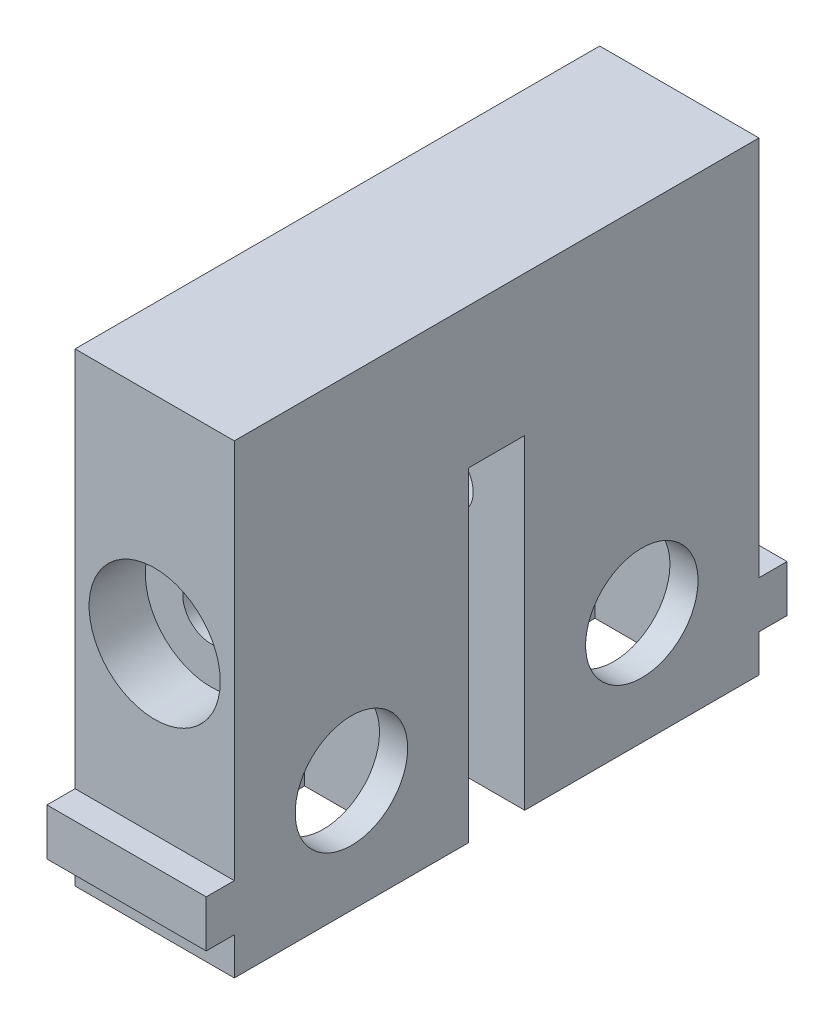
SolidWorks part; units mm, degrees
material "ABS"
ref_plane "Front Plane" through (0, 0, 0) normal (0, 0, 1) x (1, 0, 0)
ref_plane "Top Plane" through (0, 0, 0) normal (0, 1, 0) x (1, 0, 0)
ref_plane "Right Plane" through (0, 0, 0) normal (1, 0, 0) x (0, 0, -1)
sketch "Sketch1" plane through (0, 0, 0) normal (1, 0, 0) x (0, 0, -1)
  line L0 (-28, 0) -> (28, 0) construction
  line L1 (-28, -7.6538) -> (-28, 0)
  line L2 (-28, 18) -> (28, 18)
  line L3 (28, 0) -> (28, -7.6538)
  line L4 (28, -31.6539) -> (3, -31.6538)
  line L5 (3, -31.6538) -> (3, 3)
  line L6 (3, 3) -> (-3, 3)
  line L7 (-3, 3) -> (-3, -31.6538)
  line L8 (-3, -31.6538) -> (-28, -31.6539)
  line L9 (-28, -31.6539) -> (-3, -7.6538) construction
  line L10 (-3, -7.6538) -> (-28, -7.6538) construction
  line L11 (-28, -7.6538) -> (-3, -31.6538) construction
  line L12 (3, -31.6538) -> (28, -7.6538) construction
  line L13 (28, -7.6538) -> (3, -7.6538) construction
  line L14 (3, -7.6538) -> (28, -31.6539) construction
  line L15 (-28, -7.6538) -> (-28, -22.6539)
  line L16 (28, -7.6538) -> (28, -22.6539)
  line L17 (-28, -27.6539) -> (-31, -27.6539)
  line L18 (-31, -27.6539) -> (-31, -22.6539)
  line L19 (-31, -22.6539) -> (-28, -22.6539)
  line L20 (28, -27.6539) -> (31, -27.6539)
  line L21 (31, -27.6539) -> (31, -22.6539)
  line L22 (31, -22.6539) -> (28, -22.6539)
  line L23 (-28, -27.6539) -> (-28, -31.6539)
  line L24 (28, -27.6539) -> (28, -31.6539)
  line L25 (-28, 0) -> (-28, 18)
  line L26 (-15.5, -30.0462) -> (-6.5, -24.85) construction
  line L27 (-6.5, -24.85) -> (-6.5, -14.4577)
  line L28 (-6.5, -14.4577) -> (-15.5, -9.2615)
  line L29 (-15.5, -9.2615) -> (-24.5, -14.4577)
  line L30 (-24.5, -14.4577) -> (-24.5, -24.85)
  line L31 (-24.5, -24.85) -> (-15.5, -30.0462) construction
  line L32 (15.5, -30.0462) -> (24.5, -24.85) construction
  line L33 (24.5, -24.85) -> (24.5, -14.4577)
  line L34 (24.5, -14.4577) -> (15.5, -9.2615)
  line L35 (15.5, -9.2615) -> (6.5, -14.4577)
  line L36 (6.5, -14.4577) -> (6.5, -24.85)
  line L37 (6.5, -24.85) -> (15.5, -30.0462) construction
  line L38 (28, 0) -> (28, 18)
  line L39 (-6.5, -24.85) -> (-6.5, -31.6538)
  line L40 (-24.5, -24.85) -> (-24.5, -31.6539)
  line L41 (-25.8923, -31.6539) -> (-5.1077, -31.6538)
  line L42 (6.5, -24.85) -> (6.5, -31.6538)
  line L43 (5.1077, -31.6538) -> (25.8923, -31.6539)
  line L44 (24.5, -24.85) -> (24.5, -31.6539)
  circle A0 centre (-15.5, -19.6539) radius 6
  circle A1 centre (15.5, -19.6539) radius 6
  circle A2 centre (-15.5, -19.6539) radius 9 construction
  circle A3 centre (15.5, -19.6539) radius 9 construction
  dimension "D1" = 12
  dimension "D5" = 18
  dimension "D2" = 24
  dimension "D3" = 3
  dimension "D4" = 5
  dimension "D6" = 25
  dimension "D7" = 4
  dimension "D8" = 22.6539
  dimension "D9" = 15
  dimension "D10" = 3
  dimension "D11" = 6
extrude "Boss-Extrude2" add sketch "Sketch1" against normal blind 8.5 and the other way blind 8.5 contours L3 L38 L2 L25 L1 L15 L19 L18 L17 L23 L8 L7 L6 L5 L4 L24 L20 L21 L22 L16 L31 L30 L29 L28 L27 L26 L37 L36 L35 L34 L33 L32 | L30 L31 L26 L27 L28 L29 A0 | L36 L37 L32 L33 L34 L35 A1 region at (0, -3.8269, 27.2057) region at (0, -28.2519, 24.2127) region at (0, -31.3665, -15.5)
extrude "Cut-Extrude1" cut sketch "Sketch1<4>" against normal blind 5.5 and the other way blind 5.5 contours L30 L31 L26 L27 L28 L29 A0 | L36 L37 L32 L33 L34 L35 A1 region at (0, -28.2519, 24.2127) region at (0, -31.3665, -15.5)
sketch "Sketch1<4>" plane through (0, 0, 0) normal (1, 0, 0) x (0, 0, -1) same geometry as "Sketch1"
sketch "Sketch3" plane through (0, 0, 28) normal (0, 0, 1) x (1, 0, 0)
  line L0 (0, 0) -> (-8.5, 0) construction
  line L1 (-8.5, -22.6538) -> (-8.5, 18) construction
  line L2 (-8.5, -10) -> (8.5, -10) construction
  line L3 (8.5, -22.6538) -> (8.5, 18) construction
  line L4 (-8.5, 0) -> (8.5, -10) construction
  line L5 (0, 0) -> (-8.5, -10) construction
  circle A0 centre (0, -5) radius 3
  circle A1 centre (0, -5) radius 7
  dimension "D2" = 6
  dimension "D3" = 14
  dimension "D1" = 10
extrude "Cut-Extrude2" cut sketch "Sketch3" against normal through all and the other way through all contours A0 region at (0, -5, 28)
extrude "Cut-Extrude3" cut sketch "Sketch3<3>" against normal blind 6 contours A1 A0 region at (-6.802, -5, 28)
sketch "Sketch3<3>" plane through (0, 0, 28) normal (0, 0, 1) x (1, 0, 0) same geometry as "Sketch3"
sketch "Sketch4" plane through (0, 0, -28) normal (0, 0, -1) x (-1, 0, 0)
  line L0 (8.5, 18) -> (-8.5, 18) construction
  line L1 (5.7735, -5) -> (2.8868, 0)
  line L2 (2.8868, 0) -> (-2.8868, 0)
  line L3 (-2.8868, 0) -> (-5.7735, -5)
  line L4 (-5.7735, -5) -> (-2.8868, -10)
  line L5 (-2.8868, -10) -> (2.8868, -10)
  line L6 (2.8868, -10) -> (5.7735, -5)
  circle A0 centre (0, -5) radius 5 construction
  dimension "D1" = 10
extrude "Cut-Extrude4" cut sketch "Sketch4" against normal blind 10
ref_point "CableCentre"
equation "\"StrutHeight\"=37.3077"
equation "\"D8@Sketch1\"=\"StrutHeight\"/2+4"
equation "\"CarriagePulleyDiameter\"=10"
equation "\"D1@Sketch3\"=\"CarriagePulleyDiameter\""
